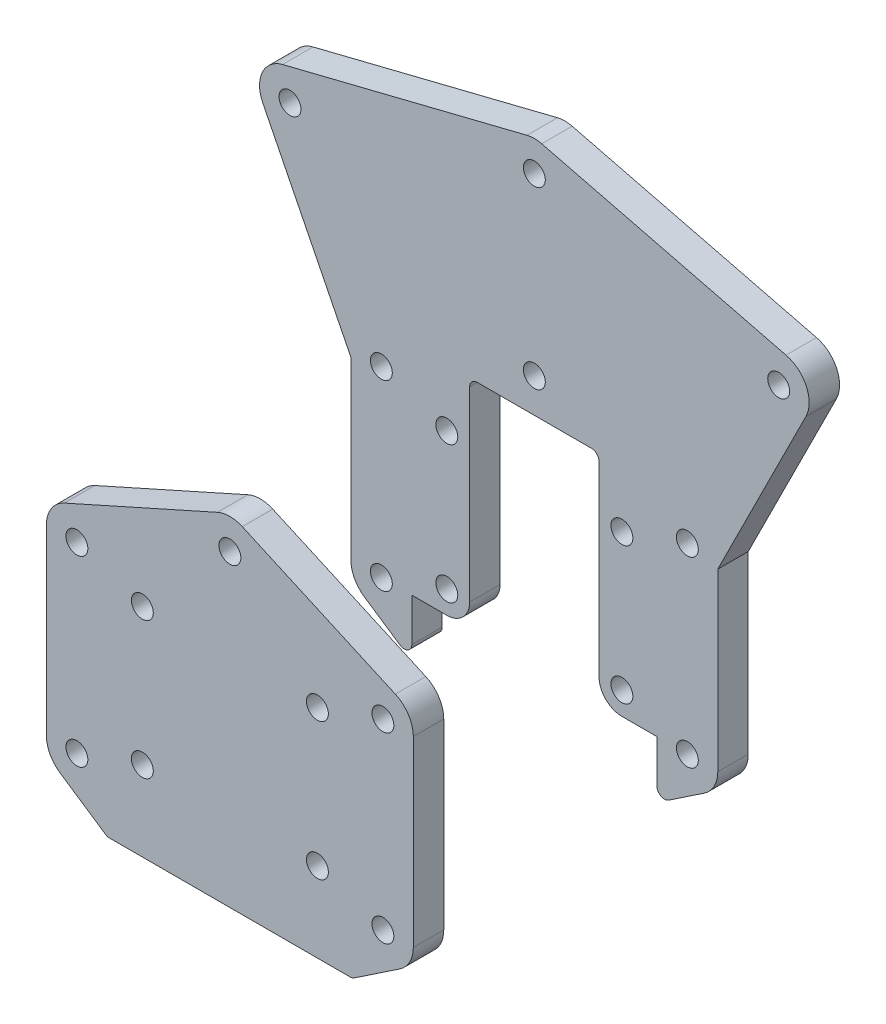
SolidWorks part; units mm, degrees
note: The reader was unsure of these and kept them because the rebuilt part matched: shared geometry of "Sketch1<3>", "Sketch4<3>".
ref_plane "Front Plane" through (0, 0, 0) normal (0, 0, 1) x (1, 0, 0)
ref_plane "Top Plane" through (0, 0, 0) normal (0, 1, 0) x (1, 0, 0)
ref_plane "Right Plane" through (0, 0, 0) normal (1, 0, 0) x (0, 0, -1)
sketch "Sketch1" plane through (0, 0, 0) normal (0, 0, 1) x (1, 0, 0)
  line L0 (-18.2562, -28.575) -> (18.2563, -28.575) construction
  line L1 (-23.0187, -9.525) -> (-23.0188, -19.05) construction
  line L3 (-25.5587, -19.05) -> (25.5587, -19.05)
  line L4 (-25.5587, -19.05) -> (-25.5588, -25.4)
  line L5 (-18.2562, -28.575) -> (18.2563, -28.575) construction
  line L6 (-23.0187, -9.525) -> (-23.0188, -19.05) construction
  line L8 (0, -28.575) -> (0, 0) construction
  line L9 (-158.75, -72.686) -> (-158.75, 26.374) construction
  line L10 (-23.0187, 0) -> (-23.0187, -9.525) construction
  line L11 (-25.5588, -25.4) -> (-31.9088, -25.4)
  line L12 (-23.0187, 0) -> (-23.0187, -9.525) construction
  line L13 (-38.2588, -19.05) -> (-38.2588, 19.05)
  line L14 (-165.1, -4.106) -> (-165.1, -42.206) construction
  line L15 (-31.9088, -19.05) -> (-31.9088, 19.05) construction
  line L16 (-31.9088, -19.05) -> (-165.1, -42.206) construction
  line L17 (-31.9088, 19.05) -> (-165.1, -4.106) construction
  line L18 (-13.4937, -12.3063) -> (-11.9062, -12.3063) construction
  line L19 (-11.9062, 12.3063) -> (-13.4937, 12.3063) construction
  line L20 (-13.4937, -12.3063) -> (-11.9062, -12.3063) construction
  line L21 (-11.9062, 12.3063) -> (-13.4937, 12.3063) construction
  line L22 (-13.4937, 12.3063) -> (-13.4937, -12.3063) construction
  line L23 (-13.4937, 0) -> (-31.9088, 0) construction
  line L24 (-31.9088, 0) -> (-165.1, -23.156) construction
  line L25 (-158.75, -72.686) -> (-158.75, 26.374) construction
  line L26 (-158.75, -23.156) -> (-165.1, -23.156) construction
  line L27 (-25.5588, -19.05) -> (-25.5588, -30.9562) construction
  line L28 (-37.5884, 16.2102) -> (-56.6384, 54.3102)
  line L29 (-50.9588, 63.5) -> (50.9588, 63.5)
  line L30 (37.5884, 16.2102) -> (56.6384, 54.3102)
  line L31 (38.2588, -19.05) -> (38.2588, 19.05)
  line L32 (25.5588, -25.4) -> (31.9088, -25.4)
  line L33 (25.5587, -19.05) -> (25.5588, -25.4)
  line L34 (-25.5588, -30.9562) -> (25.5588, -30.9562) construction
  line L35 (-25.5588, -30.9562) -> (25.5588, -30.9562)
  line L36 (-25.5588, -30.9562) -> (-35.4463, -24.3234)
  line L37 (25.5588, -30.9562) -> (35.4463, -24.3234)
  line L38 (-25.5588, -25.4) -> (-25.5588, -30.9562)
  line L39 (25.5588, -25.4) -> (25.5588, -30.9562)
  line L40 (-52.4943, 63.3115) -> (-1.5356, 76.0115)
  line L41 (52.4943, 63.3115) -> (1.5356, 76.0115)
  circle A0 centre (-31.9088, 19.05) radius 6.35 construction
  arc A1 (-50.9588, 63.5) -> (-56.6384, 54.3102) centre (-50.9588, 57.15) ccw
  circle A4 centre (-165.1, -4.106) radius 2.286
  circle A5 centre (-165.1, -42.206) radius 2.286
  circle A6 centre (-31.9088, -19.05) radius 2.286
  circle A7 centre (-31.9088, 19.05) radius 2.286
  arc A8 (-31.9088, -12.7) -> (-25.5587, -19.05) centre (-31.9088, -19.05) ccw
  circle A9 centre (-18.2563, -14.2875) radius 2.286 construction
  circle A10 centre (-18.2563, -14.2875) radius 2.286
  circle A11 centre (-50.9588, 57.15) radius 2.286
  arc A12 (50.9588, 63.5) -> (56.6384, 54.3102) centre (50.9588, 57.15) cw
  arc A13 (31.9088, -12.7) -> (25.5587, -19.05) centre (31.9088, -19.05) cw
  circle A14 centre (18.2563, -14.2875) radius 2.286
  circle A15 centre (31.9088, -19.05) radius 2.286
  circle A16 centre (31.9088, 19.05) radius 2.286
  circle A17 centre (50.9588, 57.15) radius 2.286
  circle A18 centre (0, 69.85) radius 6.35
  circle A19 centre (0, 69.85) radius 2.286
  point P3 (-31.9088, 0)
  point P48 (0, 63.5)
  point P58 (0, -19.05)
  dimension "D1" = 4.572
  dimension "D2" = 12.7
  dimension "D5" = 12.7
  dimension "D6" = 4.572
  dimension "D9" = 12.7
  dimension "D3" = 38.1
  dimension "D4" = 6.35
  dimension "D7" = 38.1
  dimension "D8" = 19.05
extrude "Boss-Extrude1" add sketch "Sketch1" along normal blind 6.35
extrude "Boss-Extrude2" add sketch "Sketch1<3>" against normal blind 6.35 from surface at -57.15 separate body
sketch "Sketch1<3>" plane through (0, 0, 0) normal (0, 0, 1) x (1, 0, 0) same geometry as "Sketch1"
fillet "Fillet1" radius 1.5875 2 edges at (25.5588, -30.9562, -60.325) (-25.5588, -30.9562, -60.325)
fillet "Fillet2" radius 1.5875 2 edges at (25.5588, -30.9562, 3.175) (-25.5588, -30.9562, 3.175)
sketch "Sketch3" plane through (0, 0, -63.5) normal (0, 0, -1) x (-1, 0, 0)
  line L0 (11.9062, 26.1938) -> (-11.9062, 26.1938)
  line L16 (-18.2563, -28.575) -> (18.2563, -28.575)
  line L17 (18.2563, -28.575) -> (18.2563, -19.05)
  line L18 (18.2563, -19.05) -> (23.0187, -19.05)
  line L19 (23.0187, -19.05) -> (23.0187, -9.525)
  line L20 (23.0187, -9.525) -> (18.2563, -9.525)
  line L21 (18.2563, -9.525) -> (18.2563, 0)
  line L22 (18.2563, 0) -> (13.4937, 0)
  line L23 (13.4937, 0) -> (13.4937, -24.6062)
  line L24 (11.9062, -26.1937) -> (-11.9062, -26.1937)
  line L25 (-13.4937, -24.6062) -> (-13.4937, 0)
  line L26 (-13.4937, 0) -> (-18.2563, 0)
  line L27 (-18.2563, 0) -> (-18.2563, -9.525)
  line L28 (-18.2563, -9.525) -> (-23.0188, -9.525)
  line L29 (-23.0188, -9.525) -> (-23.0188, -19.05)
  line L30 (-23.0188, -19.05) -> (-18.2563, -19.05)
  line L31 (-18.2563, -19.05) -> (-18.2563, -28.575)
  line L39 (13.4937, 24.6063) -> (13.4937, -24.6062)
  line L40 (11.9062, -26.1937) -> (-11.9062, -26.1937)
  line L41 (-13.4937, -24.6062) -> (-13.4937, 24.6063)
  line L42 (-13.4937, 0) -> (-18.2563, 0) construction
  arc A0 (11.9062, 26.1938) -> (13.4937, 24.6063) centre (11.9062, 24.6063) cw
  arc A1 (-13.4937, 24.6063) -> (-11.9062, 26.1938) centre (-11.9062, 24.6063) cw
  arc A2 (11.9062, -26.1937) -> (13.4937, -24.6062) centre (11.9062, -24.6062) ccw
  arc A3 (-13.4937, -24.6062) -> (-11.9062, -26.1937) centre (-11.9062, -24.6062) ccw
  arc A4 (11.9062, -26.1937) -> (13.4937, -24.6062) centre (11.9062, -24.6062) ccw
  arc A5 (-13.4937, -24.6062) -> (-11.9062, -26.1937) centre (-11.9062, -24.6062) ccw
  dimension "D1" = 0
extrude "Cut-Extrude1" cut sketch "Sketch3" against normal blind 7.62
fillet "Fillet3" radius 4.7625 2 edges at (13.4937, -19.05, -60.325) (-13.4937, -19.05, -60.325)
sketch "Sketch4" plane through (0, 0, 6.35) normal (0, 0, 1) x (1, 0, 0)
  line L0 (-34.5038, 24.8455) -> (-2.595, 39.133)
  line L1 (34.5038, 24.8455) -> (2.595, 39.133)
  line L2 (-38.2588, 17.551) -> (-38.2588, 19.05)
  line L3 (38.2588, 17.551) -> (38.2588, 19.05)
  line L4 (38.2588, 17.551) -> (125.4224, 90.4023)
  line L5 (125.4224, 90.4023) -> (-79.2317, 82.9092)
  line L6 (-79.2317, 82.9092) -> (-98.2459, 9.0775)
  line L7 (-98.2459, 9.0775) -> (-38.2588, 17.551)
  circle A0 centre (-31.9088, 19.05) radius 6.35
  circle A1 centre (31.9088, 19.05) radius 6.35
  circle A2 centre (0, 33.3375) radius 6.35
  circle A3 centre (0, 33.3375) radius 2.286
  circle A4 centre (-18.2563, -14.2875) radius 2.286 construction
  circle A5 centre (-18.2563, 14.2875) radius 2.286
  circle A6 centre (18.2563, 14.2875) radius 2.286
  point P29 (18.2563, -14.2875)
  point P30 (-18.2563, -14.2875)
  point P31 (0, 0)
  point P34 (0, 0)
  point P35 (0, 0)
  point P36 (125.4224, 90.4023)
  dimension "D1" = 12.7
  dimension "D2" = 4.572
  dimension "D3" = 47.625
  dimension "D4" = 28.575
extrude "Cut-Extrude2" cut sketch "Sketch4" against normal blind 9.525
extrude "Cut-Extrude3" cut sketch "Sketch4<3>" against normal through all both and the other way through all contours A3 | A5 | A6
sketch "Sketch4<3>" plane through (0, 0, 6.35) normal (0, 0, 1) x (1, 0, 0) same geometry as "Sketch4"
